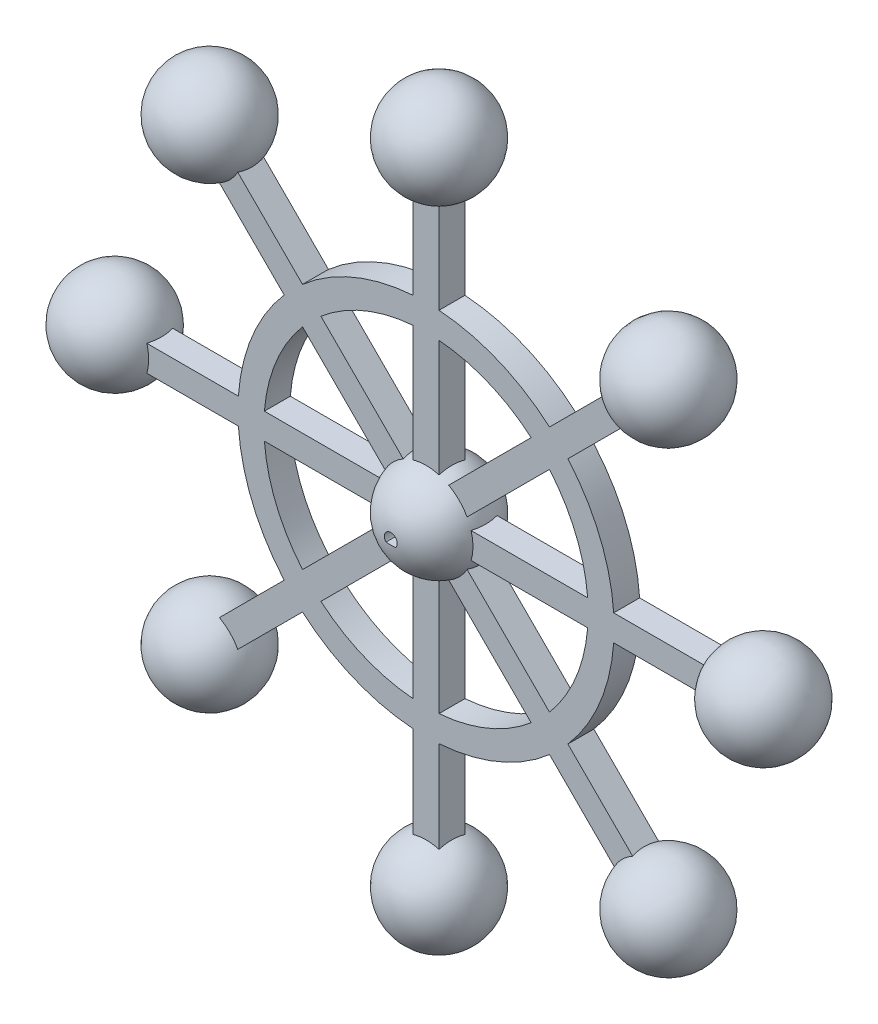
SolidWorks part; units mm, degrees
ref_plane "Front Plane" through (0, 0, 0) normal (0, 0, 1) x (1, 0, 0)
ref_plane "Top Plane" through (0, 0, 0) normal (0, 1, 0) x (1, 0, 0)
ref_plane "Right Plane" through (0, 0, 0) normal (1, 0, 0) x (0, 0, -1)
sketch "Sketch1" plane through (0, 0, 0) normal (0, 0, 1) x (1, 0, 0)
  line L0 (0, 19.05) -> (0, -19.05)
  arc A0 (0, -19.05) -> (0, 19.05) centre (0, 0) ccw
  dimension "D1" = 38.1
revolve "Revolve1" add sketch "Sketch1" angle 360 about L0
sketch "Sketch2" plane through (0, 0, 0) normal (0, 0, 1) x (1, 0, 0)
  line L0 (0, 0) -> (127, 0) construction
  line L1 (0, -5.08) -> (127, -5.08)
  line L2 (0, 5.08) -> (127, 5.08)
  line L3 (127, 5.08) -> (127, -5.08)
  line L4 (0, 5.08) -> (0, -5.08)
  dimension "D1" = 127
  dimension "D2" = 5.08
  dimension "D3" = 5.08
extrude "Boss-Extrude1" add sketch "Sketch2" along normal blind 5.08 and the other way blind 5.08
sketch "Sketch3" plane through (0, 0, 0) normal (0, 1, 0) x (1, 0, 0)
  line L0 (0, 0) -> (0, 8.1282) construction
pattern_circular "CirPattern1" count 8 over 360 about axis through (0, 0, 0) along (0, 0, -1) of "Boss-Extrude1" reverse direction yes
sketch "Sketch5" plane through (0, 0, -5.08) normal (0, 0, -1) x (-1, 0, 0)
  circle A0 centre (0, 0) radius 63.5
  circle A1 centre (0, 0) radius 73.66
  dimension "D1" = 127
  dimension "D2" = 10.16
extrude "Boss-Extrude2" add sketch "Sketch5" against normal blind 10.16
sketch "Sketch6" plane through (0, 0, -5.08) normal (0, 0, -1) x (-1, 0, 0)
  line L0 (-1.8555, -1.6783) -> (1.8555, -1.6783)
  arc A0 (1.8555, -1.6783) -> (-1.8555, -1.6783) centre (0, 0) ccw
  dimension "D1" = 5.0038
  dimension "D2" = 3.711
extrude "Cut-Extrude1" cut sketch "Sketch6" against normal through all and the other way through all
sketch "Sketch7" plane through (0, 0, 0) normal (0, 0, 1) x (1, 0, 0)
  line L0 (5.08, 127) -> (-5.08, 127) construction
  line L1 (0, 107.95) -> (0, 146.05)
  arc A0 (0, 107.95) -> (0, 146.05) centre (0, 127) ccw
  dimension "D1" = 38.1
revolve "Revolve2" add sketch "Sketch7" angle 360 about L1
pattern_circular "CirPattern2" count 8 over 360 about axis through (0, 0, 0) along (0, 0, -1) of "Revolve2"
